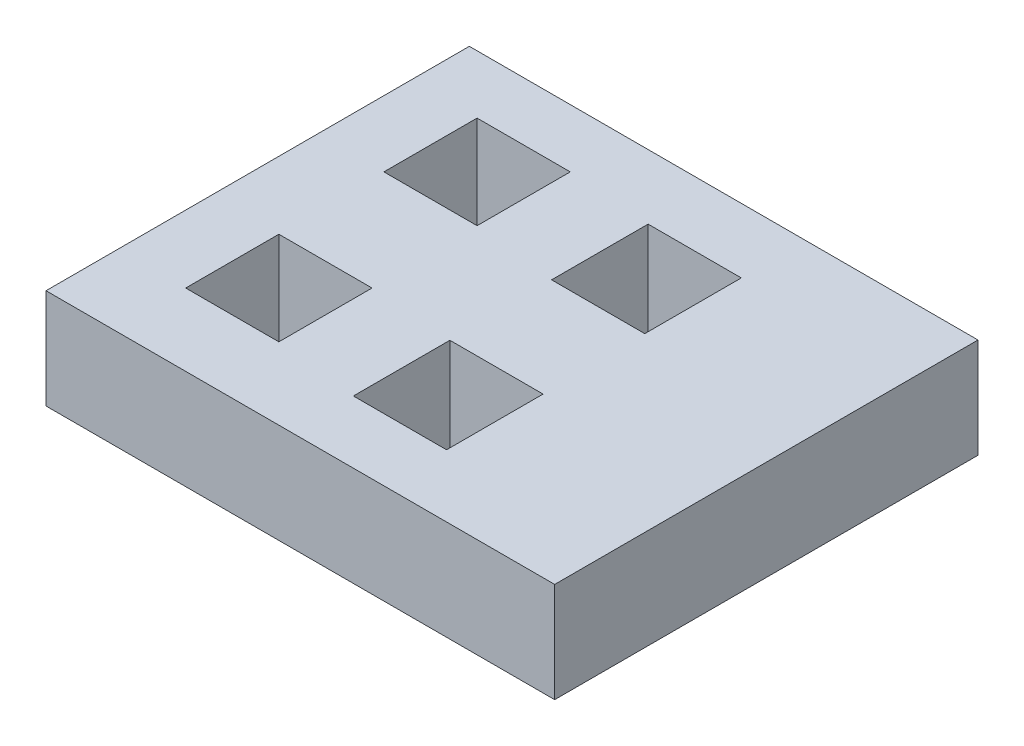
SolidWorks part; units mm, degrees
ref_plane "Front Plane" through (0, 0, 0) normal (0, 0, 1) x (1, 0, 0)
ref_plane "Top Plane" through (0, 0, 0) normal (0, 1, 0) x (1, 0, 0)
ref_plane "Right Plane" through (0, 0, 0) normal (1, 0, 0) x (0, 0, -1)
sketch "Sketch1" plane through (0, 0, 0) normal (0, 1, 0) x (1, 0, 0)
  line L959 (-5.9459, 6.8798) -> (9.3377, 6.8798)
  line L960 (-5.9459, 6.8798) -> (-5.9459, -5.8395)
  line L961 (-5.9459, -5.8395) -> (9.3377, -5.8395)
  line L962 (9.3377, 6.8798) -> (9.3377, -5.8395)
  line L978 (-3.9175, -0.8712) -> (-1.1175, -0.8712)
  line L979 (-3.9619, 5.1288) -> (-1.1619, 5.1288)
  line L980 (-3.9619, 5.1288) -> (-3.9619, 2.3288)
  line L981 (-3.9619, 2.3288) -> (-1.1619, 2.3288)
  line L982 (-1.1619, 5.1288) -> (-1.1619, 2.3288)
  line L983 (-3.9175, -0.8712) -> (-3.9175, -3.6712)
  line L984 (-3.9175, -3.6712) -> (-1.1175, -3.6712)
  line L985 (-1.1175, -0.8712) -> (-1.1175, -3.6712)
  line L986 (1.4111, -1.061) -> (4.2111, -1.061)
  line L987 (1.3666, 4.939) -> (4.1666, 4.939)
  line L988 (1.3666, 4.939) -> (1.3666, 2.039)
  line L989 (1.3666, 2.039) -> (4.1666, 2.039)
  line L990 (4.1666, 4.939) -> (4.1666, 2.039)
  line L991 (1.4111, -1.061) -> (1.4111, -3.961)
  line L992 (1.4111, -3.961) -> (4.2111, -3.961)
  line L993 (4.2111, -1.061) -> (4.2111, -3.961)
  dimension "D3" = 2.9
  dimension "D4" = 2.9
  dimension "D2" = 3.2
  dimension "D5" = 3.1
  dimension "D12" = 2.8
  dimension "D13" = 2.8
  dimension "D14" = 2.8
  dimension "D15" = 2.8
extrude "Boss-Extrude1" add sketch "Sketch1" along normal blind 3
